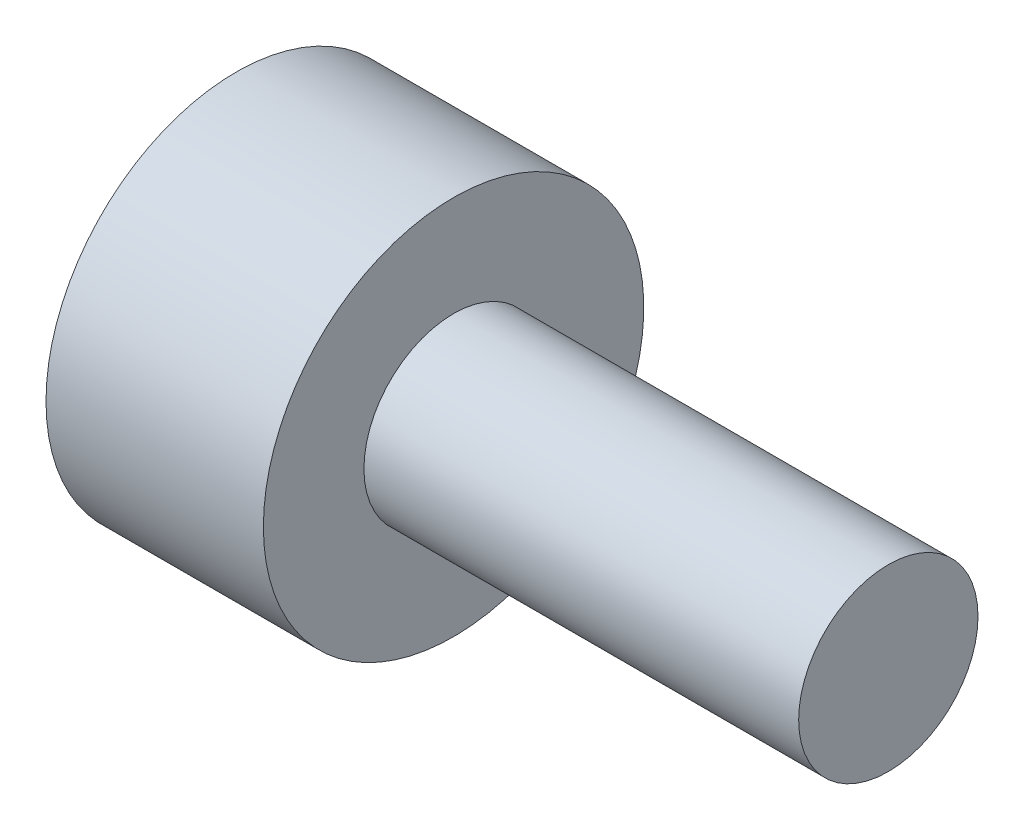
SolidWorks part; units mm, degrees
ref_plane "Front Plane" through (0, 0, 0) normal (0, 0, 1) x (1, 0, 0)
ref_plane "Top Plane" through (0, 0, 0) normal (0, 1, 0) x (1, 0, 0)
ref_plane "Right Plane" through (0, 0, 0) normal (1, 0, 0) x (0, 0, -1)
sketch "Screw Sketch" plane through (0, 0, 0) normal (0, 0, 1) x (1, 0, 0)
  line L0 (-1000, 0) -> (1000, 0) construction
  line L1 (-4, 0) -> (-4, 3.5)
  line L2 (-4, 3.5) -> (0, 3.5)
  line L3 (0, 3.5) -> (0, 1.65)
  line L4 (0, 1.65) -> (8, 1.65)
  line L5 (8, 1.65) -> (8, 0)
  line L6 (8, 0) -> (-4, 0)
revolve "Screw" add sketch "Screw Sketch" angle 360 about L0
ref_axis "Engine Axis" through (8.6, 0, 0) along (-1, 0, 0)
ref_plane "Head Top" through (-4, 0, 0) normal (1, 0, 0) x (0, 0, -1)
sketch "Socket Sketch" plane through (-4, 0, 0) normal (1, 0, 0) x (0, 0, -1)
  line L0 (1.7321, 0) -> (0.866, 1.5)
  line L1 (0.866, 1.5) -> (-0.866, 1.5)
  line L2 (-0.866, 1.5) -> (-1.7321, 0)
  line L3 (-1.7321, 0) -> (-0.866, -1.5)
  line L4 (-0.866, -1.5) -> (0.866, -1.5)
  line L5 (0.866, -1.5) -> (1.7321, 0)
extrude "Socket" cut sketch "Socket Sketch" along normal blind 2
